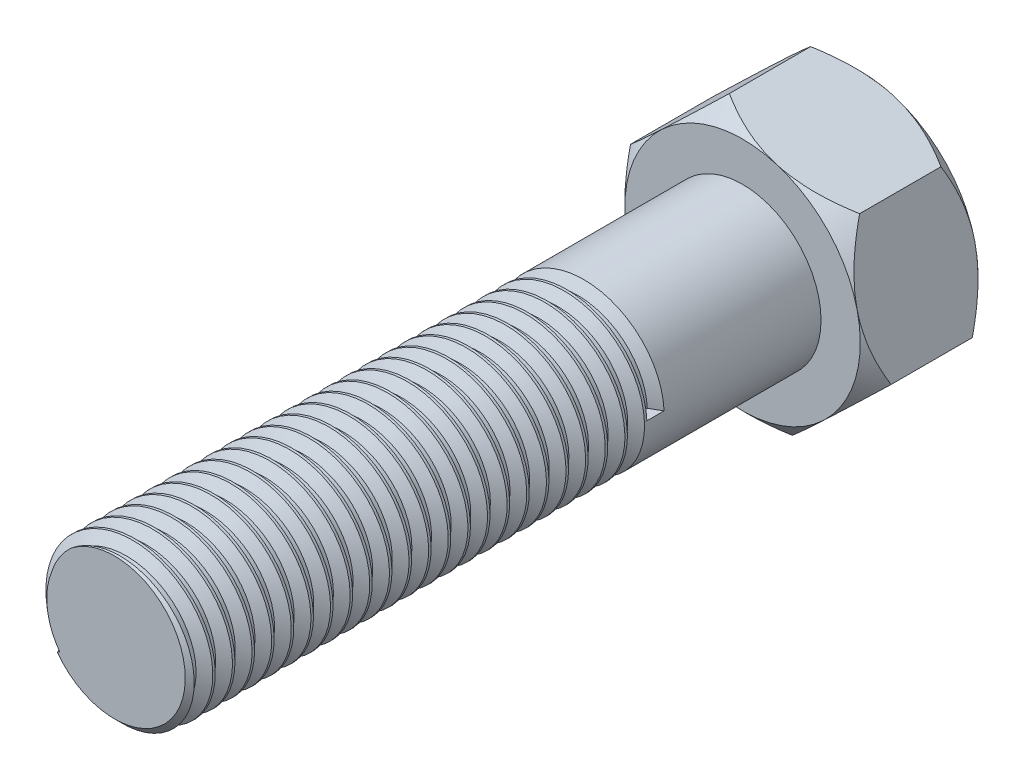
SolidWorks part; units mm, degrees
ref_plane "Front Plane" through (0, 0, 0) normal (0, 0, 1) x (1, 0, 0)
ref_plane "Top Plane" through (0, 0, 0) normal (0, 1, 0) x (1, 0, 0)
ref_plane "Right Plane" through (0, 0, 0) normal (1, 0, 0) x (0, 0, -1)
sketch "Sketch2" plane through (0, 0, 0) normal (0, 0, 1) x (1, 0, 0)
  line L3 (12.5922, 11.8927) -> (-4.0032, 16.8515)
  line L4 (-4.0032, 16.8515) -> (-16.5955, 4.9589)
  line L5 (-16.5955, 4.9589) -> (-12.5922, -11.8927)
  line L6 (-12.5922, -11.8927) -> (4.0032, -16.8515)
  line L7 (4.0032, -16.8515) -> (16.5955, -4.9589)
  line L8 (16.5955, -4.9589) -> (12.5922, 11.8927)
  circle A0 centre (0, 0) radius 15 construction
  point P0 (4.2945, 14.3721)
  dimension "D1" = 30
extrude "Boss-Extrude1" add sketch "Sketch2" along normal blind 15
sketch "Sketch4" plane through (0, 0, 15) normal (0, 0, 1) x (1, 0, 0)
  circle A0 centre (0, 0) radius 15
extrude "Cut-Extrude5" cut sketch "Sketch4" against normal blind 15 draft 45 flip side to cut
sketch "Sketch5" plane through (0, 0, 0) normal (0, 0, -1) x (-1, 0, 0)
  circle A0 centre (0, 0) radius 15
extrude "Cut-Extrude6" cut sketch "Sketch5" against normal blind 15 draft 45 flip side to cut
sketch "Sketch6" plane through (0, 0, 15) normal (0, 0, 1) x (1, 0, 0)
  circle A0 centre (0, 0) radius 10
  dimension "D1" = 20
extrude "Boss-Extrude2" add sketch "Sketch6" along normal blind 80
chamfer "Chamfer3" distance 1 angle 45 1 edges at (10, 0, 95)
thread "Thread3" pitch 2.5 method cut profile "Thread Profile4" start angle 0, offset 20, length 0, pitch 2.5, diameter 20
ref_plane "Plane4" through (10, 0, 35) normal (0, -1, 0) x (1, 0, 0)
sketch "Thread Profile4" plane through (10, 0, 35) normal (0, -1, 0) x (1, 0, 0)
  line L0 (0, 0) -> (0, 2.5) construction
  line L11 (0, 0) -> (0, 2.1875)
  line L12 (0, 2.1875) -> (-1.3532, 1.4062)
  line L13 (-1.3532, 1.4062) -> (-1.3532, 0.7812)
  line L15 (-1.3532, 0.7812) -> (0, 0)
  line L17 (-1.3532, 1.0937) -> (0, 1.0937) construction
  point P2 (0, 0)
  dimension "Pitch" = 2.5
  dimension "Profile_Angle" = 60
  dimension "Profile_Land" = 0.625
  dimension "Profile_Height" = 1.3532
